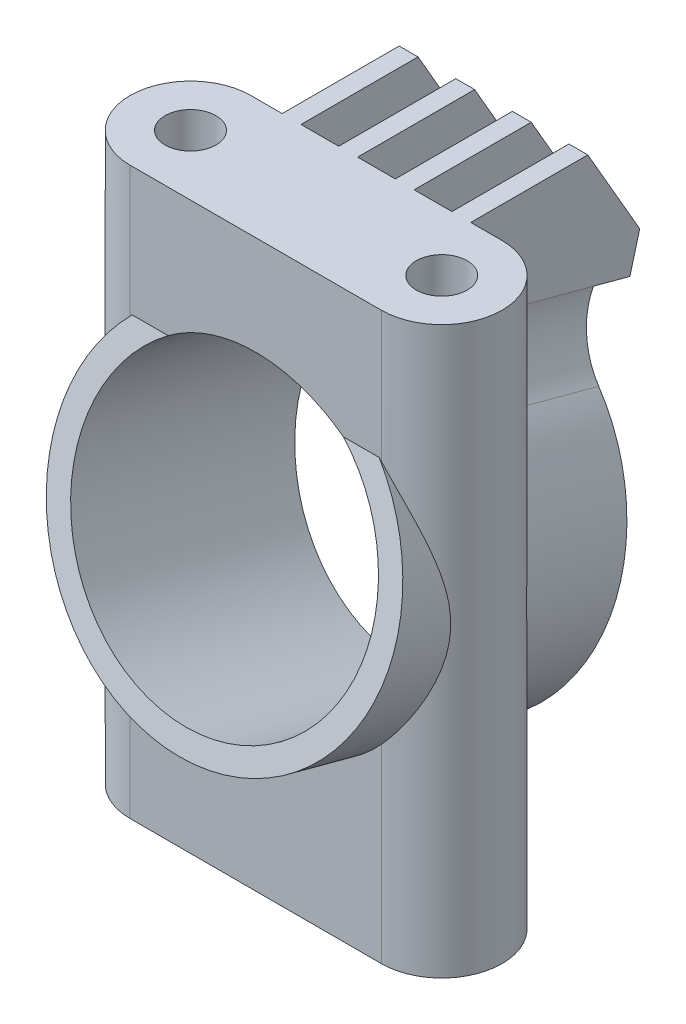
SolidWorks part; units mm, degrees
ref_plane "Ebene vorne" through (0, 0, 0) normal (0, 0, 1) x (1, 0, 0)
ref_plane "Ebene oben" through (0, 0, 0) normal (0, 1, 0) x (1, 0, 0)
ref_plane "Ebene rechts" through (0, 0, 0) normal (1, 0, 0) x (0, 0, -1)
sketch "Skizze1" plane through (0, 0, 0) normal (0, 1, 0) x (1, 0, 0)
  line L0 (-6.66, 0) -> (6.66, 0) construction
  line L1 (-6.66, 3.2) -> (6.66, 3.2)
  line L2 (-6.66, -3.2) -> (6.66, -3.2)
  arc A0 (-6.66, 3.2) -> (-6.66, -3.2) centre (-6.66, 0) ccw
  arc A1 (6.66, -3.2) -> (6.66, 3.2) centre (6.66, 0) ccw
  point P3 (0, 0)
  dimension "D1" = 3.2
  dimension "D2" = 13.32
extrude "Grundkörper" add sketch "Skizze1" along normal blind 30
ref_plane "Ebene CamNeigung" through (0, 0.8, 2.9856) normal (0, 0.2588, 0.9659) x (1, 0, 0)
sketch "Skizze2" plane through (0, 0.8, 2.9856) normal (0, 0.2588, 0.9659) x (1, 0, 0)
  line L0 (0, -0.8282) -> (0, 15.1718) construction
  line L1 (-6.66, -0.8282) -> (6.66, -0.8282) construction
  circle A0 centre (0, 15.1718) radius 7.9
  dimension "D1" = 15.8
  dimension "D2" = 16
extrude "ObjektivBohrung" cut sketch "Skizze2" against normal through all and the other way through all
sketch "Skizze5" plane through (0, 0.8, 2.9856) normal (0, 0.2588, 0.9659) x (1, 0, 0)
  circle A0 centre (0, 15.1718) radius 7.9
  circle A1 centre (0, 15.1718) radius 9.15
  dimension "D1" = 15.8
  dimension "D2" = 18.3
extrude "ObjektivRing" add sketch "Skizze5" against normal blind 6.3 and the other way blind 6
sketch "Skizze6" plane through (0, -0.8306, -3.0997) normal (0, -0.2588, -0.9659) x (-1, 0, 0)
  line L0 (0, 25.5218) -> (0, 15.1718) construction
  line L1 (-11.9603, 4.8218) -> (11.9603, 4.8218) construction
  line L2 (-11.9603, 4.8218) -> (-11.9603, 25.5218) construction
  line L3 (-11.9603, 25.5218) -> (11.9603, 25.5218) construction
  line L4 (11.9603, 4.8218) -> (11.9603, 25.5218) construction
  line L5 (-11.9603, 4.8218) -> (11.9603, 25.5218) construction
  line L6 (-11.9603, 25.5218) -> (11.9603, 4.8218) construction
  line L7 (-5, 25.5218) -> (-3.8238, 23.4845)
  line L8 (-5, 25.5218) -> (5, 25.5218)
  line L9 (5, 25.5218) -> (3.8238, 23.4845)
  arc A0 (6.66, 21.4461) -> (-6.66, 21.4461) centre (0, 15.1718) ccw construction
  arc A2 (-3.8238, 23.4845) -> (3.8238, 23.4845) centre (0, 15.1718) cw
  circle A3 centre (0, 15.1718) radius 9.15 construction
  point P0 (0, 15.1718)
  dimension "D1" = 20.7
  dimension "D2" = 10
  dimension "D3" = 60
extrude "CamVerdrehschutzAnsatz" add sketch "Skizze6" against normal up to next
sketch "Skizze8" plane through (0, 24.6521, -6.6055) normal (0, 0.9659, -0.2588) x (1, 0, 0)
  line L0 (-5, -4.791) -> (-5, 5.209)
  line L2 (-5, -3.5257) -> (-5, 3.209) construction
  line L3 (-5, 5.209) -> (5, 5.209)
  line L4 (5, 5.209) -> (5, -4.791)
  line L6 (5, -4.791) -> (-5, -4.791)
  line L7 (-5, 3.209) -> (5, 3.209) construction
  line L8 (5, -3.5257) -> (5, 3.209) construction
  dimension "D1" = 2
  dimension "D2" = 10
extrude "CamVerdrehSchutzNase" add sketch "Skizze8" along normal blind 2
sketch "Skizze9" plane through (0, -0.8306, -3.0997) normal (0, -0.2588, -0.9659) x (-1, 0, 0)
  line L0 (-4.4226, 26.5218) -> (4.4226, 26.5218)
  line L2 (-5, 25.5218) -> (5, 25.5218) construction
  line L3 (-4.4226, 26.5218) -> (-2.7556, 23.6344)
  line L4 (0, 25.5218) -> (0, 15.1718) construction
  line L5 (-5, 25.5218) -> (-3.8238, 23.4845) construction
  line L6 (-5, 25.5218) -> (-3.8238, 23.4845) construction
  line L7 (4.4226, 26.5218) -> (2.7556, 23.6344)
  line L8 (5, 25.5218) -> (-5, 25.5218) construction
  arc A0 (2.7556, 23.6344) -> (-2.7556, 23.6344) centre (0, 15.1718) ccw
  circle A1 centre (0, 15.1718) radius 7.9 construction
  dimension "D2" = 1
  dimension "D1" = 1
  dimension "D3" = 1
extrude "GerichtsEinsparungVerdrehschutz" cut sketch "Skizze9" against normal up to surface and the other way blind 1.5 up to face at (0, 25.6284, -3.2)
fillet "Verrundung1" radius 4 1 edges at (0, 27.6352, -3.2)
fillet "Verrundung2" radius 4 4 edges at (3.8238, 22.6546, -6.189) (-3.8238, 22.6546, -6.189) (-2.7556, 22.8046, -6.2084) (2.7556, 22.8046, -6.2084)
fillet "Verrundung4" radius 2 5 edges at (4.2874, 26.3575, -3.2) (2.595, 24.5453, -3.2) (0, 24.0635, -3.2) (-4.2874, 26.3575, -3.2) (-2.595, 24.5453, -3.2)
sketch "Skizze10" plane through (0, 30, 0) normal (0, 1, 0) x (1, 0, 0)
  line L0 (6.66, 3.2) -> (5, 3.2) construction
  line L1 (-5, 12.1547) -> (-4, 12.1547)
  line L2 (-5, 12.1547) -> (-5, 3.2)
  line L3 (-5, 3.2) -> (-4, 3.2)
  line L4 (-4, 12.1547) -> (-4, 3.2)
  line L5 (5, 3.2) -> (-5, 3.2) construction
  line L6 (5, 12.1547) -> (4, 12.1547)
  line L7 (5, 12.1547) -> (5, 3.2)
  line L8 (5, 3.2) -> (4, 3.2)
  line L9 (4, 12.1547) -> (4, 3.2)
  line L10 (5, 12.1547) -> (-5, 12.1547) construction
  line L11 (-2, 12.1547) -> (-1, 12.1547)
  line L12 (-2, 12.1547) -> (-2, 3.2)
  line L13 (-2, 3.2) -> (-1, 3.2)
  line L14 (-1, 12.1547) -> (-1, 3.2)
  line L15 (-4, 7.6774) -> (-2, 7.6774) construction
  line L16 (1, 12.1547) -> (2, 12.1547)
  line L17 (1, 12.1547) -> (1, 3.2)
  line L18 (1, 3.2) -> (2, 3.2)
  line L19 (2, 12.1547) -> (2, 3.2)
  line L20 (-1, 7.6774) -> (1, 7.6774) construction
  line L21 (2, 7.6774) -> (4, 7.6774) construction
  dimension "D1" = 1
extrude "Aufsatz-Linear austragen5" add sketch "Skizze10" against normal up to next
sketch "Skizze11" plane through (-5, 0, 0) normal (-1, 0, 0) x (0, 0, 1)
  line L0 (-12.1547, 25.2358) -> (-9.4041, 30)
  line L1 (-12.1547, 30) -> (-3.2, 30) construction
  line L2 (-9.4041, 30) -> (-12.1547, 30)
  line L3 (-12.1547, 30) -> (-12.1547, 25.2358)
  dimension "D1" = 60
extrude "Schnitt-Linear austragen5" cut sketch "Skizze11" against normal through all
sketch "Skizze3" plane through (0, 30, 0) normal (0, 1, 0) x (1, 0, 0)
  circle A0 centre (-6.66, 0) radius 1.35
  circle A1 centre (6.66, 0) radius 1.35
  dimension "D1" = 2.7
extrude "TopPlatteBohrung" cut sketch "Skizze3" against normal blind 8
sketch "Skizze4" plane through (0, 0, 0) normal (0, -1, 0) x (1, 0, 0)
  circle A0 centre (-6.66, 0) radius 1.35
  circle A1 centre (6.66, 0) radius 1.35
  dimension "D1" = 2.7
extrude "BottomPlatteBohrung" cut sketch "Skizze4" against normal blind 8
